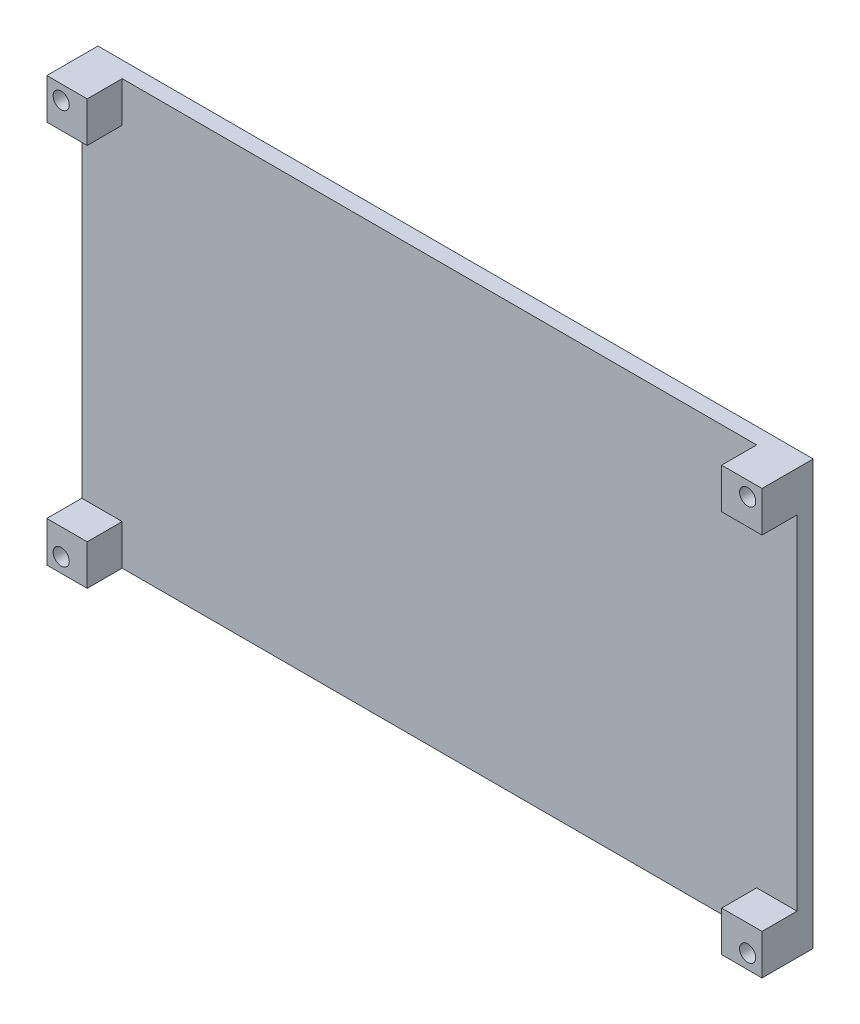
SolidWorks part; units mm, degrees
note: The reader was unsure of these and kept them because the rebuilt part matched: shared geometry of "Sketch1<3>".
ref_plane "Front Plane" through (0, 0, 0) normal (0, 0, 1) x (1, 0, 0)
ref_plane "Top Plane" through (0, 0, 0) normal (0, 1, 0) x (1, 0, 0)
ref_plane "Right Plane" through (0, 0, 0) normal (1, 0, 0) x (0, 0, -1)
sketch "Sketch1" plane through (0, 0, 0) normal (0, 0, 1) x (1, 0, 0)
  line L0 (0, -1000) -> (0, 49000) construction
  line L1 (-66.42, -39.37) -> (66.42, -39.37)
  line L2 (-66.42, -39.37) -> (-66.42, 39.37)
  line L3 (-66.42, 39.37) -> (66.42, 39.37)
  line L4 (66.42, -39.37) -> (66.42, 39.37)
  line L5 (-66.42, -39.37) -> (66.42, 39.37) construction
  line L6 (-66.42, 39.37) -> (66.42, -39.37) construction
  line L7 (-1000, 0) -> (49000, 0) construction
  line L8 (-66.42, 39.37) -> (-58.92, 31.87) construction
  line L9 (58.92, 39.37) -> (58.92, 31.87)
  line L10 (-66.42, 39.37) -> (-58.92, 39.37)
  line L11 (-66.42, 39.37) -> (-66.42, 31.87)
  line L12 (-66.42, 31.87) -> (-58.92, 31.87)
  line L13 (-58.92, 39.37) -> (-58.92, 31.87)
  line L14 (66.42, 31.87) -> (58.92, 31.87)
  line L15 (66.42, -31.87) -> (58.92, -31.87)
  line L16 (58.92, -39.37) -> (58.92, -31.87)
  line L17 (-58.92, -39.37) -> (-58.92, -31.87)
  line L18 (-66.42, -31.87) -> (-58.92, -31.87)
  circle A0 centre (-63.75, 36.7) radius 1.5
  circle A1 centre (63.75, 36.7) radius 1.5
  circle A2 centre (63.75, -36.7) radius 1.5
  circle A3 centre (-63.75, -36.7) radius 1.5
  point P0 (0, 0)
  dimension "D3" = 3
  dimension "D1" = 132.84
  dimension "D2" = 78.74
  dimension "D5" = 2.67
  dimension "D4" = 2.67
  dimension "D7" = 7.5
extrude "Boss-Extrude1" add sketch "Sketch1" along normal mid plane 3 contours L2 L18 L17 L1 L16 L15 L4 L14 L9 L3 L13 L12 | L18 L2 L1 L17 A3 | L13 L3 L2 L12 A0 | L14 L4 L3 L9 A1 | L16 L1 L4 L15 A2
extrude "Boss-Extrude2" add sketch "Sketch1<3>" along normal blind 8 contours L18 L2 L1 L17 A3 | L13 L3 L2 L12 A0 | L14 L4 L3 L9 A1 | L16 L1 L4 L15 A2
sketch "Sketch1<3>" plane through (0, 0, 0) normal (0, 0, 1) x (1, 0, 0) same geometry as "Sketch1"
sketch "Sketch2" plane through (0, 0, -1.5) normal (0, 0, -1) x (-1, 0, 0)
  line L0 (-16.975, -39.37) -> (-6.975, -39.37)
  line L1 (-16.975, -39.37) -> (-16.975, -14.37)
  line L2 (-16.975, -14.37) -> (-6.975, -14.37)
  line L3 (-6.975, -39.37) -> (-6.975, -14.37)
  line L4 (0, 0) -> (0, -39.37) construction
  line L5 (66.42, -39.37) -> (-66.42, -39.37) construction
  line L6 (16.975, -14.37) -> (6.975, -14.37)
  line L7 (6.975, -39.37) -> (6.975, -14.37)
  line L8 (16.975, -39.37) -> (16.975, -14.37)
  line M9 (-66.42, -39.37) -> (66.42, -39.37)
  dimension "D1" = 10
  dimension "D2" = 6.975
  dimension "D3" = 25
extrude "Boss-Extrude3" add sketch "Sketch2" along normal blind 35 contours L3 L2 L1 M9 | L8 L6 L7 M9
sketch "Sketch3" plane through (-16.975, 0, 0) normal (-1, 0, 0) x (0, 0, 1)
  line L0 (-36.5, -39.37) -> (-1.5, -14.37)
extrude "Cut-Extrude1" cut sketch "Sketch3" against normal blind 65 and the other way through all
sketch "Sketch4" plane through (16.975, 0, 0) normal (1, 0, 0) x (0, 0, -1)
  line L0 (1.5, -39.37) -> (1.5, -14.37) construction
  line L2 (36.5, -39.37) -> (1.5, -39.37) construction
  circle A0 centre (16.5, -31.37) radius 2
  dimension "D1" = 4
  dimension "D3" = 8
  dimension "D2" = 15
extrude "Cut-Extrude2" cut sketch "Sketch4" against normal blind 65
fillet "Fillet1" radius 7.5 2 edges at (11.975, -39.37, -36.5) (-11.975, -39.37, -36.5)
